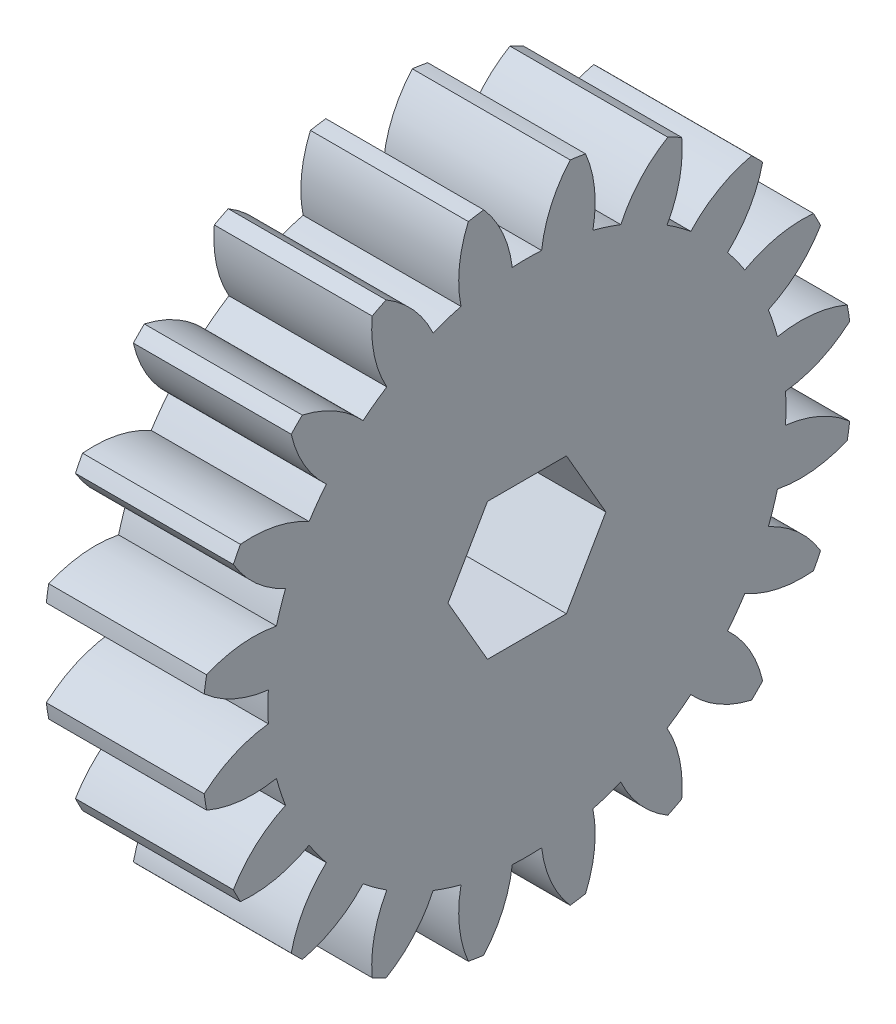
SolidWorks part; units mm, degrees
ref_plane "Plane1" through (0, 0, 0) normal (0, 0, 1) x (1, 0, 0)
ref_plane "Plane2" through (0, 0, 0) normal (0, 1, 0) x (1, 0, 0)
ref_plane "Plane3" through (0, 0, 0) normal (1, 0, 0) x (0, 0, -1)
sketch "HoldingSke" plane through (0, 0, 0) normal (0, 1, 0) x (1, 0, 0)
  line L0 (0, 0) -> (0.6265, -0.228)
  line L1 (-15, 0) -> (100, 0) construction
  line L2 (0, 0) -> (-2.1039, 2.3779)
  line L3 (0, 0) -> (-11.863, 4.5341)
  line L4 (0, 0) -> (8.1152, 2.9537)
  line L5 (0, 0) -> (-46.8476, -17.4728)
  line L6 (0, 0) -> (-9.9476, -6.7116)
  line L7 (-2.1039, 2.3779) -> (8.6586, 51.2059)
  line L8 (-76.2, 54.61) -> (-75.3, 54.61)
  line L9 (-71.009, 38.7566) -> (-53.1078, 45.2721)
  line L10 (-76.2, 71.12) -> (104.1128, 71.12)
  line L11 (0, 0) -> (-12, 0)
  line L12 (-76.2, 101.6) -> (-76.147, 101.6)
  line L13 (24.9733, 27.94) -> (52.9518, 28.4284)
  line L14 (24.9733, 27.94) -> (24.9743, 27.94)
  line L15 (24.9733, 27.94) -> (100.4006, 29.5858)
  line L16 (-63.627, -1.5) -> (-12.827, -1.5)
  circle A0 centre (0, 0) radius 2.5
  circle A1 centre (0, 0) radius 13.124
  circle A2 centre (0, 0) radius 37.5
  circle A3 centre (0, 0) radius 2.5
  dimension "MHD" = 26.248
  dimension "Hub_dia" = 75
  dimension "Bore" = 5
  dimension "MBD" = 5
  dimension "Num_teeth" = 20
  dimension "Pitch" = 0.6667
  dimension "Overall_len" = 50
  dimension "Show_teeth" = 20
  dimension "Thickness" = 12
  dimension "OAL" = 50.0001
  dimension "T_dim" = 0.9
  dimension "Ap" = 20
  dimension "H" = 19.05
  dimension "Pitch_radius" = 180.3128
  dimension "Width" = 12
  dimension "Backlash" = 0.053
  dimension "Addendum_fac" = 1
  dimension "Dedendum_fac" = 1.25
  dimension "Clearance_fac" = 0.25
  dimension "Dedendum_add" = 0.001
  dimension "Module" = 1.5
sketch "BasProSke" plane through (0, 0, 0) normal (0, 1, 0) x (1, 0, 0)
  line L0 (-10, 0) -> (60, 0) construction
  line L1 (0, 0) -> (0, 16.5)
  line L2 (0, 0) -> (8, 0)
  line L3 (8, 0) -> (8, 16.5)
  line L4 (8, 16.5) -> (0, 16.5)
  dimension "Thickness" = 8
  dimension "Diameter" = 33
revolve "Base-Revolve" add sketch "BasProSke" angle 360 about L0
sketch "TooCutSke" plane through (0, 0, 0) normal (1, 0, 0) x (0, 0, -1)
  line L1 (0, 0) -> (0, 107) construction
  line L2 (0, 0) -> (-1.2696, 14.9462) construction
  line L3 (0, 0) -> (-4.6808, 29.5532) construction
  line L4 (-1.2696, 14.9462) -> (-2.3404, 14.7766) construction
  arc A0 (0.7438, 13.1029) -> (-0.7438, 13.1029) centre (0, 0) ccw
  arc A1 (2.21, 16.377) -> (-2.21, 16.377) centre (0, 0) ccw
  circle A2 centre (0, 0) radius 15 construction
  circle A3 centre (0, 0) radius 14.0954 construction
  arc A4 (-0.7438, 13.1029) -> (-2.21, 16.377) centre (-6.7025, 12.3999) ccw
  arc A5 (2.21, 16.377) -> (0.7438, 13.1029) centre (6.7025, 12.3999) ccw
  dimension "Root_dia" = 26.248
  dimension "Overcut_dia" = 33.0508
  dimension "Pitch_dia" = 30
  dimension "Base_dia" = 28.1908
  dimension "Flank_rad" = 6
  dimension "Half_ang" = 9
  dimension "Half_CT" = 1.0841
extrude "ToothCut" cut sketch "TooCutSke" along normal through all
fillet "Breaks" [suppressed] radius 0.03 tangent propagation no
fillet "RootFillets" [suppressed] radius 0.376
pattern_circular "TeethCuts" count 20 every 18 about axis through (-10, 0, 0) along (1, 0, 0) of "ToothCut", "RootFillets", "Breaks"
sketch "HubNeaOneSke" plane through (0, 0, 0) normal (-1, 0, 0) x (0, 0, 1)
  circle A0 centre (0, 0) radius 13.124
  dimension "Diameter" = 26.248
extrude "HubNearOne" [suppressed] add sketch "HubNeaOneSke" along normal blind 42.0001
sketch "HubNeaBotSke" plane through (0, 0, 0) normal (-1, 0, 0) x (0, 0, 1)
  circle A0 centre (0, 0) radius 13.124
  dimension "Diameter" = 26.248
extrude "HubNearBoth" [suppressed] add sketch "HubNeaBotSke" along normal blind 21
ref_plane "FarPln" through (8, 0, 0) normal (1, 0, 0) x (0, 0, -1)
sketch "HubFarSke" plane through (8, 0, 0) normal (1, 0, 0) x (0, 0, -1)
  circle A0 centre (0, 0) radius 13.124
  dimension "Diameter" = 26.248
extrude "HubFar" [suppressed] add sketch "HubFarSke" along normal blind 21
sketch "BorSke" plane through (0, 0, 0) normal (1, 0, 0) x (0, 0, -1)
  circle A0 centre (0, 0) radius 2.5
  dimension "Diameter" = 5
extrude "Bore" cut sketch "BorSke" along normal mid plane 100.0001
sketch "KeySke" plane through (0, 0, 0) normal (1, 0, 0) x (0, 0, -1)
  line L0 (-1, 0) -> (-1, 3.4)
  line L1 (-1, 3.4) -> (1, 3.4)
  line L2 (1, 3.4) -> (1, 0)
  line L3 (0, 0) -> (0, 34) construction
  line L4 (-1, 0) -> (1, 0)
  dimension "Offset" = 3.4
  dimension "Width" = 2
extrude "Keyway" [suppressed] cut sketch "KeySke" along normal mid plane 100.0001
pattern_circular "Keyway2" [suppressed] count 2 every 90 about axis through (-10, 0, 0) along (1, 0, 0) reverse direction yes
sketch "Sketch1" plane through (8, 0, 0) normal (1, 0, 0) x (0, 0, -1)
  line L1 (4, 0) -> (2, 3.4641)
  line L2 (2, 3.4641) -> (-2, 3.4641)
  line L3 (-2, 3.4641) -> (-4, 0)
  line L4 (-4, 0) -> (-2, -3.4641)
  line L5 (-2, -3.4641) -> (2, -3.4641)
  line L6 (2, -3.4641) -> (4, 0)
  circle A0 centre (0, 0) radius 3.4641 construction
  circle A1 centre (0, 0) radius 4 construction
  dimension "D1" = 8
extrude "Cut-Extrude1" cut sketch "Sketch1" against normal through all
ref_plane "Plane4" through (8, 16.2303, -2.9711) normal (1, 0, 0) x (0, 0, -1)
sketch "Sketch2" plane through (8, 16.2303, -2.9711) normal (1, 0, 0) x (0, 0, -1)
  line L0 (-6.9711, -16.2303) -> (-4.9711, -19.6944) construction
  line L1 (-4.9711, -19.6944) -> (-0.9711, -19.6944) construction
  line L2 (-0.9711, -19.6944) -> (1.0289, -16.2303) construction
  line L3 (1.0289, -16.2303) -> (-0.9711, -12.7662) construction
  line L4 (-0.9711, -12.7662) -> (-4.9711, -12.7662) construction
  line L5 (-4.9711, -12.7662) -> (-6.9711, -16.2303) construction
  line L6 (-4.9711, -12.7662) -> (-6.9711, -16.2303)
  line L7 (-0.9711, -12.7662) -> (-4.9711, -12.7662)
  line L8 (1.0289, -16.2303) -> (-0.9711, -12.7662)
  line L9 (-0.9711, -19.6944) -> (1.0289, -16.2303)
  line L10 (-4.9711, -19.6944) -> (-0.9711, -19.6944)
  line L11 (-6.9711, -16.2303) -> (-4.9711, -19.6944)
  circle A0 centre (-2.9711, -16.2303) radius 7.5
  dimension "D1" = 15
extrude "Boss-Extrude1" [suppressed] add sketch "Sketch2" along normal blind 2.5
sketch "Sketch3" plane through (0, 0, 0) normal (-1, 0, 0) x (0, 0, 1)
  line L0 (2, 3.4641) -> (4, 0) construction
  line L1 (-2, 3.4641) -> (2, 3.4641) construction
  line L2 (-4, 0) -> (-2, 3.4641) construction
  line L3 (-2, -3.4641) -> (-4, 0) construction
  line L4 (2, -3.4641) -> (-2, -3.4641) construction
  line L5 (4, 0) -> (2, -3.4641) construction
  line L6 (4, 0) -> (2, -3.4641)
  line L7 (2, -3.4641) -> (-2, -3.4641)
  line L8 (-2, -3.4641) -> (-4, 0)
  line L9 (-4, 0) -> (-2, 3.4641)
  line L10 (-2, 3.4641) -> (2, 3.4641)
  line L11 (2, 3.4641) -> (4, 0)
  circle A0 centre (0, 0) radius 7.5
  dimension "D1" = 15
extrude "Boss-Extrude2" [suppressed] add sketch "Sketch3" along normal blind 2.5
equation "' \"Module@HoldingSke\" = 6.35"
equation "' \"Num_teeth@HoldingSke\" = 12"
equation "' \"Ap@HoldingSke\" =  20"
equation "' \"Ap@HoldingSke\" = 20"
equation "' \"Width@HoldingSke\" = 0.5 * 25.4"
equation "' \"Hub_dia@HoldingSke\"= 1 * 25.4"
equation "' \"Hub_dia@HoldingSke\" = 1 * 25.4"
equation "' \"Overall_len@HoldingSke\" = 1.0 * 25.4"
equation "' \"Bore@HoldingSke\" = 0.75 * 25.4"
equation "' \"T_dim@HoldingSke\" = 0.1 * 25.4"
equation "' \"Width@KeySke\" = 0.25 * 25.4"
equation "' \"Show_teeth@HoldingSke\" = 13"
equation "' \"Backlash@HoldingSke\" = 0.009 * 25.4"
equation "' \"Addendum_fac@HoldingSke\" = 1.0"
equation "' \"Dedendum_fac@HoldingSke\" = 1.25"
equation "' \"Dedendum_add@HoldingSke\" = 0.00005 * 25.4"
equation "' \"Clearance_fac@HoldingSke\" = 0.25"
equation "\"Pitch@HoldingSke\" = 1 / \"Module@HoldingSke\""
equation "\"Overcut_dia@TooCutSke\" = (\"Num_teeth@HoldingSke\" + 2 * \"Addendum_fac@HoldingSke\") / \"Pitch@HoldingSke\" + 0.002 * 25.4"
equation "\"Pitch_dia@TooCutSke\" = \"Num_teeth@HoldingSke\" / \"Pitch@HoldingSke\""
equation "\"Base_dia@TooCutSke\" = \"Num_teeth@HoldingSke\" / \"Pitch@HoldingSke\" * cos((\"Ap@HoldingSke\"  * 3.14159265 / 180))"
equation "\"Root_dia@TooCutSke\" = (\"Num_teeth@HoldingSke\" + 2) / \"Pitch@HoldingSke\" - 2 * (\"Addendum_fac@HoldingSke\" + \"Dedendum_fac@HoldingSke\") / \"Pitch@HoldingSke\" - \"Dedendum_add@HoldingSke\" * 2"
equation "\"Half_ang@TooCutSke\" = 180 / \"Num_teeth@HoldingSke\""
equation "\"Half_CT@TooCutSke\" = \"Num_teeth@HoldingSke\" / \"Pitch@HoldingSke\" * sin((3.14159265 / 2 / \"Num_teeth@HoldingSke\")) / 2 - 7 * \"Backlash@HoldingSke\" / 4"
equation "\"Flank_rad@TooCutSke\" = \"Num_teeth@HoldingSke\" / \"Pitch@HoldingSke\" / 5"
equation "\"Radius@RootFillets\" = \"Clearance_fac@HoldingSke\" / \"Pitch@HoldingSke\" + \"Dedendum_add@HoldingSke\""
equation "\"Break_rad@Breaks\" = 0.02 / \"Pitch@HoldingSke\""
equation "\"Thickness@HoldingSke\" = \"Width@HoldingSke\""
equation "\"OAL@HoldingSke\" = \"Thickness@HoldingSke\""
equation "\"MHD@HoldingSke\" = (\"Num_teeth@HoldingSke\" + 2) / \"Pitch@HoldingSke\" - 2 * (\"Addendum_fac@HoldingSke\" + \"Dedendum_fac@HoldingSke\")  / \"Pitch@HoldingSke\" - \"Dedendum_add@HoldingSke\" * 2"
equation "\"MBD@HoldingSke\" = (\"Num_teeth@HoldingSke\" + 2) / \"Pitch@HoldingSke\" - 2 * (\"Addendum_fac@HoldingSke\" + \"Dedendum_fac@HoldingSke\")  / \"Pitch@HoldingSke\" - \"Dedendum_add@HoldingSke\" * 2 - 0.002 * 25.4"
equation "\"MHD@HoldingSke\" = ((sgn( \"MHD@HoldingSke\" - \"Hub_dia@HoldingSke\" )-1)*( \"MHD@HoldingSke\" - \"Hub_dia@HoldingSke\" ))/-2+ \"Hub_dia@HoldingSke\""
equation "\"MBD@HoldingSke\" = ((sgn( \"MBD@HoldingSke\" - \"Bore@HoldingSke\" )-1)*( \"MBD@HoldingSke\" - \"Bore@HoldingSke\" ))/-2+ \"Bore@HoldingSke\""
equation "\"OAL@HoldingSke\" = ((sgn( \"OAL@HoldingSke\" - \"Overall_len@HoldingSke\" )+1)*( \"OAL@HoldingSke\" - \"Overall_len@HoldingSke\" ))/2 + \"Overall_len@HoldingSke\" + 0.000002 * 25.4"
equation "\"Num_teeth@TeethCuts\" = int( \"Show_teeth@HoldingSke\" ) + 1"
equation "\"Num_teeth@TeethCuts\" = ((sgn( \"Num_teeth@TeethCuts\" - \"Num_teeth@HoldingSke\" )-1)*( \"Num_teeth@TeethCuts\" - \"Num_teeth@HoldingSke\" ))/-2+ \"Num_teeth@HoldingSke\""
equation "\"Num_teeth@TeethCuts\" = ((sgn( \"Num_teeth@TeethCuts\" - 2.0)+1)*( \"Num_teeth@TeethCuts\" - 2.0))/2 +2.0"
equation "\"Angle@TeethCuts\" = 360.0 / \"Num_teeth@HoldingSke\""
equation "\"Diameter@BasProSke\" = (\"Num_teeth@HoldingSke\" + 2 * \"Addendum_fac@HoldingSke\") / \"Pitch@HoldingSke\""
equation "\"Thickness@BasProSke\"=8"
equation "' \"Fillet_rad@BasProSke\" =  \"Thickness@HoldingSke\" * 0.05"
equation "' \"Fillet_rad@BasProSke\" = \"Thickness@HoldingSke\" * 0.05"
equation "\"MHD@HoldingSke\" = ((sgn( \"MHD@HoldingSke\" - \"Root_dia@TooCutSke\" )-1)*( \"MHD@HoldingSke\" - \"Root_dia@TooCutSke\" ))/-2+ \"Root_dia@TooCutSke\""
equation "\"Diameter@HubNeaOneSke\" = \"MHD@HoldingSke\""
equation "\"Length@HubNearOne\" = \"OAL@HoldingSke\" - \"Thickness@BasProSke\""
equation "\"Diameter@HubNeaBotSke\" = \"MHD@HoldingSke\""
equation "\"Length@HubNearBoth\" = ( \"OAL@HoldingSke\" - \"Thickness@BasProSke\" ) / 2.0"
equation "\"Thickness@FarPln\" = \"Thickness@BasProSke\""
equation "\"Diameter@HubFarSke\" = \"MHD@HoldingSke\""
equation "\"Length@HubFar\" = ( \"OAL@HoldingSke\" - \"Thickness@BasProSke\" ) / 2.0"
equation "\"Diameter@BorSke\" = \"MBD@HoldingSke\""
equation "\"D1@Bore\" = \"OAL@HoldingSke\" * 2.0"
equation "\"D1@Keyway\" = \"OAL@HoldingSke\" * 2.0"
equation "\"Offset@KeySke\" = \"T_dim@HoldingSke\" + \"MBD@HoldingSke\" / 2.0"
